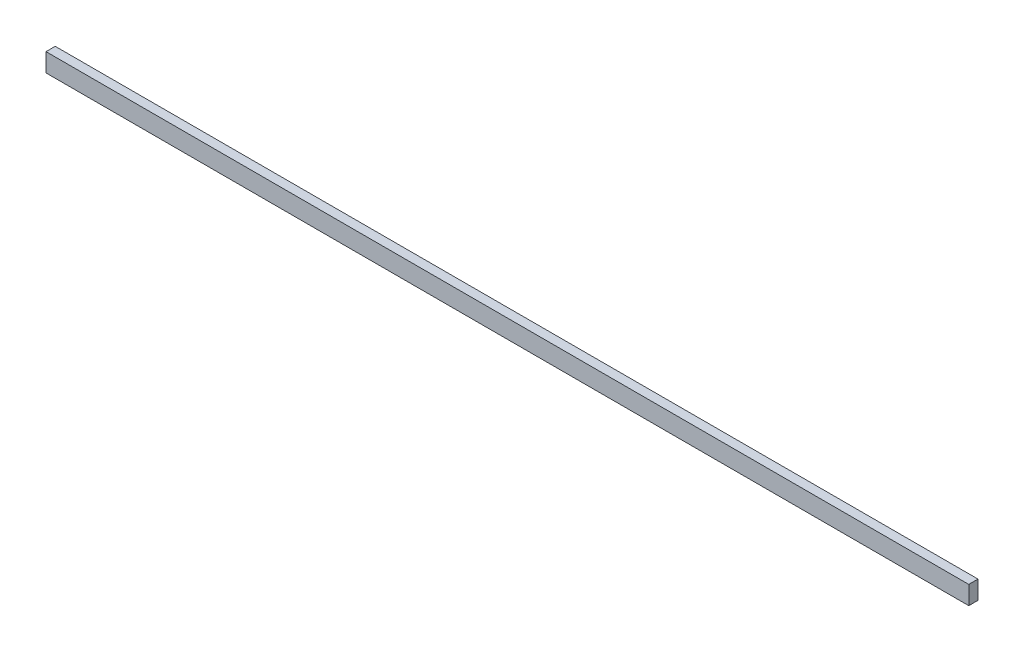
SolidWorks part; units mm, degrees
ref_plane "Front" through (0, 0, 0) normal (0, 0, 1) x (1, 0, 0)
ref_plane "Top" through (0, 0, 0) normal (0, 1, 0) x (1, 0, 0)
ref_plane "Right" through (0, 0, 0) normal (1, 0, 0) x (0, 0, -1)
other "Configuration Table"
sketch "Sketch1" plane through (0, 0, 0) normal (0, 0, 1) x (1, 0, 0)
  line L1 (0, -25.4) -> (2540, -25.4)
  line L2 (0, -25.4) -> (0, 25.4)
  line L3 (0, 25.4) -> (2540, 25.4)
  line L4 (2540, -25.4) -> (2540, 25.4)
  dimension "D1" = 2540
  dimension "D2" = 50.8
extrude "Extrude1" add sketch "Sketch1" along normal blind 25.4
sketch "Sketch3" plane through (2540, 0, 0) normal (1, 0, 0) x (0, 0, -1)
  line L0 (-42.5166, -0.1199) -> (19.7768, -0.1199)
  line L2 (-25.4, -25.4) -> (0, -25.4) construction
  dimension "D1" = 25.2801
ref_axis "Axis1" through (2540, -0.1199, -19.7768) along (0, 0, 1)
